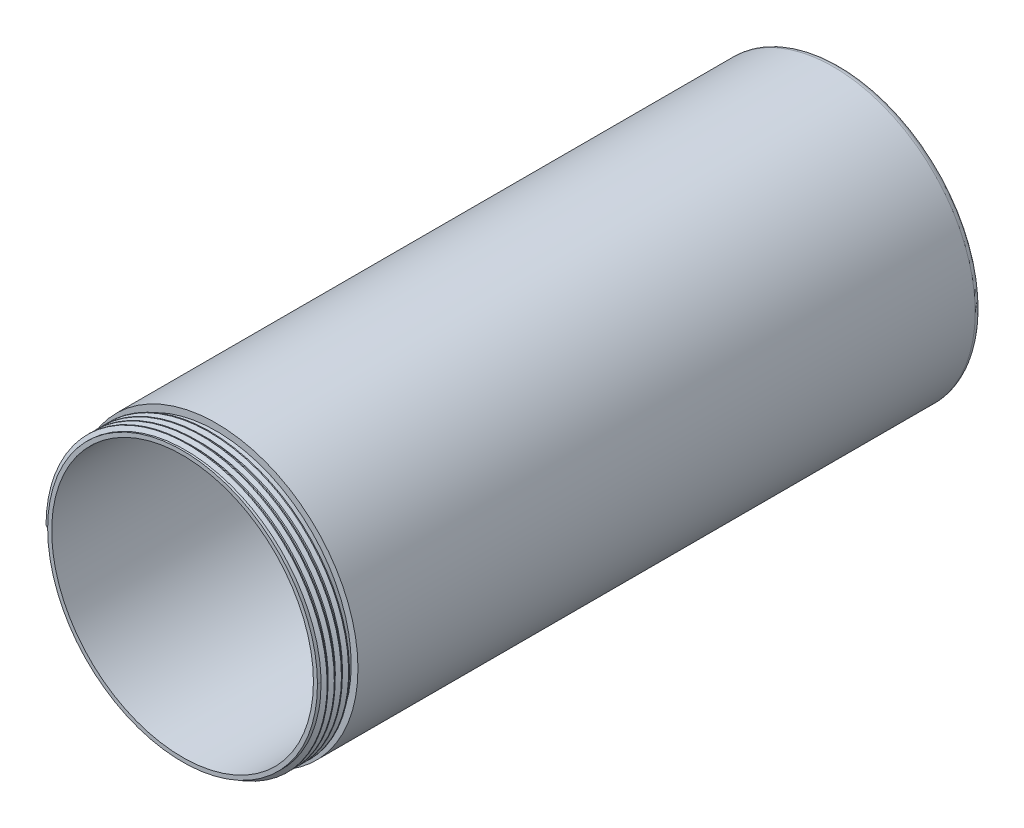
SolidWorks part; units mm, degrees
ref_plane "Front Plane" through (0, 0, 0) normal (0, 0, 1) x (1, 0, 0)
ref_plane "Top Plane" through (0, 0, 0) normal (0, 1, 0) x (1, 0, 0)
ref_plane "Right Plane" through (0, 0, 0) normal (1, 0, 0) x (0, 0, -1)
sketch "Sketch1" plane through (0, 0, 0) normal (0, 1, 0) x (1, 0, 0)
  circle A0 centre (0, 0) radius 42
  dimension "D1" = 84
extrude "Boss-Extrude1" add sketch "Sketch1" along normal blind 195 contours A0
sketch "Sketch2" plane through (0, 195, 0) normal (0, 1, 0) x (1, 0, 0)
  circle A0 centre (0, 0) radius 40
move or copy body "Body-Move/Copy1" bodies to move or copy 101 copy no translate (-42, 11.3402, 0)
move or copy body "Body-Move/Copy2" bodies to move or copy 104 copy no rotation origin (0, 108.8402, 0) rotation axis (1, 0, 0) rotation angle 90
move or copy body "Body-Move/Copy3" bodies to move or copy 105 copy no translate (-3.3007, -3.6422, -82.8031)
sketch "Sketch3" plane through (0, 0, 14.6969) normal (0, 0, 1) x (1, 0, 0)
  circle A2 centre (-45.3007, 105.198) radius 41
  circle A3 centre (-45.3007, 105.198) radius 41
  dimension "D1" = 1
fillet "Fillet1" radius 2 1 edges at (-45.3007, 63.198, -180.3031)
sketch "Sketch5" plane through (0, 0, 14.6969) normal (0, 0, 1) x (1, 0, 0)
  circle A2 centre (-45.3007, 105.198) radius 38.8
  circle A3 centre (-45.3007, 105.198) radius 38.8
  dimension "D1" = 3.2
extrude "Cut-Extrude1" cut sketch "Sketch5" against normal blind 190
sketch "Sketch6" plane through (0, 0, 14.6969) normal (0, 0, 1) x (1, 0, 0)
  circle A2 centre (-45.3007, 105.198) radius 40
  circle A3 centre (-45.3007, 105.198) radius 40
  dimension "D1" = 2
extrude "Cut-Extrude2" cut sketch "Sketch6" against normal blind 10 flip side to cut
thread "Thread1" pitch 2.1167 method extrude profile "Thread Profile1" start angle 0, offset 0, length 8, pitch 2.1167, diameter 80
ref_plane "Plane1" through (-85.3007, 105.198, 14.6969) normal (0, -1, 0) x (-1, 0, 0)
sketch "Thread Profile1" plane through (-85.3007, 105.198, 14.6969) normal (0, -1, 0) x (-1, 0, 0)
  line L0 (0, 0) -> (0, 2.1167) construction
  line L1 (0, 0) -> (1.1457, 0.6615)
  line L2 (1.1457, 0.6615) -> (1.1457, 0.926)
  line L3 (1.1457, 0.926) -> (0, 1.5875)
  line L4 (1.1457, 0.7937) -> (0, 0.7937) construction
  line L11 (0, 0) -> (0, 1.5875)
  point P2 (0, 0)
  dimension "Pitch" = 2.1167
  dimension "Profile_Angle" = 60
  dimension "Profile_Land" = 0.2646
  dimension "Profile_Height" = 1.1457
